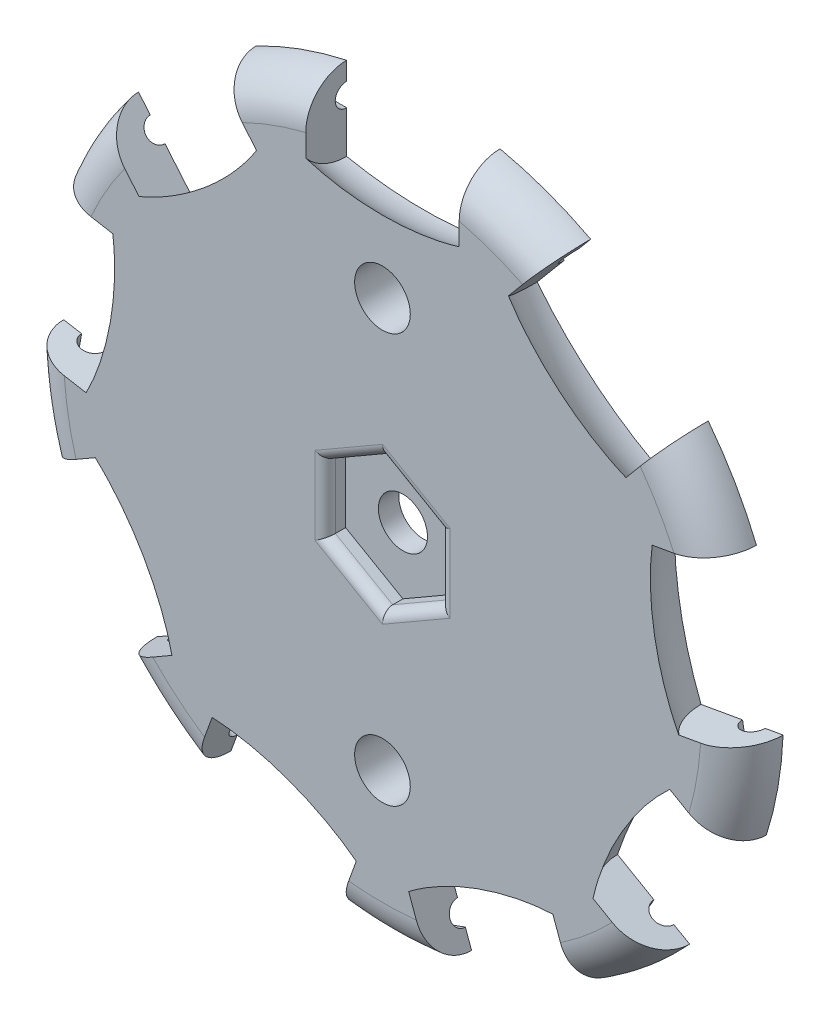
SolidWorks part; units mm, degrees
ref_plane "Front Plane" through (0, 0, 0) normal (0, 0, 1) x (1, 0, 0)
ref_plane "Top Plane" through (0, 0, 0) normal (0, 1, 0) x (1, 0, 0)
ref_plane "Right Plane" through (0, 0, 0) normal (1, 0, 0) x (0, 0, -1)
sketch "Sketch1" plane through (0, 0, 0) normal (0, 0, 1) x (1, 0, 0)
  circle A0 centre (0, 0) radius 27.94
  dimension "D1" = 55.88
extrude "Boss-Extrude1" add sketch "Sketch1" along normal blind 3.175
fillet "Fillet1" radius 3.1852 1 edges at (27.94, 0, 3.175)
sketch "Sketch2" plane through (0, 0, 3.175) normal (0, 0, 1) x (1, 0, 0)
  line L0 (0, -15.875) -> (0, 15.875) construction
  line L1 (0, 0) -> (0, 6.4682) construction
  circle A0 centre (0, 15.875) radius 2.159
  circle A1 centre (0, -15.875) radius 2.159
  circle A4 centre (0, 0) radius 1.905
  point P9 (0, 0)
  dimension "D2" = 4.318
  dimension "D4" = 3.81
  dimension "D1" = 15.875
  dimension "D3" = 2
extrude "Cut-Extrude1" cut sketch "Sketch2" against normal through all
sketch "Sketch5" plane through (0, 0, 0) normal (0, 0, 1) x (1, 0, 0)
  line L0 (-5.9531, 24.9936) -> (5.9531, 24.9936)
  line L1 (5.9531, 24.9936) -> (5.9531, 29.1545)
  line L2 (-5.9531, 24.9936) -> (-5.9531, 29.1545)
  line L3 (-5.9531, 24.9936) -> (-8.5086, 24.9936) construction
  arc A0 (-5.9531, 29.1545) -> (5.9531, 29.1545) centre (0, 0) cw
  circle A1 centre (0, 0) radius 27.94 construction
  point P5 (0, 24.9936)
  point P9 (0, 29.7561)
  dimension "D1" = 11.9062
  dimension "D2" = 24.9936
  dimension "D3" = 9.525
revolve "Cut-Revolve1" cut sketch "Sketch5" angle 360 about L3
sketch "Sketch6" plane through (0, 0, 0) normal (1, 0, 0) x (0, 0, -1)
  line L0 (0, -27.94) -> (0, 27.2984) construction
  circle A0 centre (0, 24.9936) radius 0.889
  arc A1 (-3.175, 22.3043) -> (0, 20.8327) centre (0, 24.9936) ccw construction
  dimension "D1" = 1.778
extrude "Cut-Extrude2" cut sketch "Sketch6" against normal mid plane 15.875
pattern_circular "CirPattern1" count 9 over 360 about axis through (0, 0, 0) along (0, 0, 1) of "Cut-Revolve1", "Cut-Extrude2"
sketch "Sketch8" plane through (0, 0, 3.175) normal (0, 0, 1) x (1, 0, 0)
  line L1 (0, 5.1326) -> (-4.445, 2.5663)
  line L2 (-4.445, 2.5663) -> (-4.445, -2.5663)
  line L3 (-4.445, -2.5663) -> (0, -5.1326)
  line L4 (0, -5.1326) -> (4.445, -2.5663)
  line L5 (4.445, -2.5663) -> (4.445, 2.5663)
  line L6 (4.445, 2.5663) -> (0, 5.1326)
  circle A0 centre (0, 0) radius 4.445 construction
  dimension "D1" = 8.89
extrude "Cut-Extrude4" cut sketch "Sketch8" against normal blind 1.5875
fillet "Fillet2" radius 0.7937 6 edges at (-2.2225, 3.8495, 3.175) (-4.445, 0, 3.175) (-2.2225, -3.8495, 3.175) (2.2225, -3.8495, 3.175) (4.445, 0, 3.175) (2.2225, 3.8495, 3.175)
